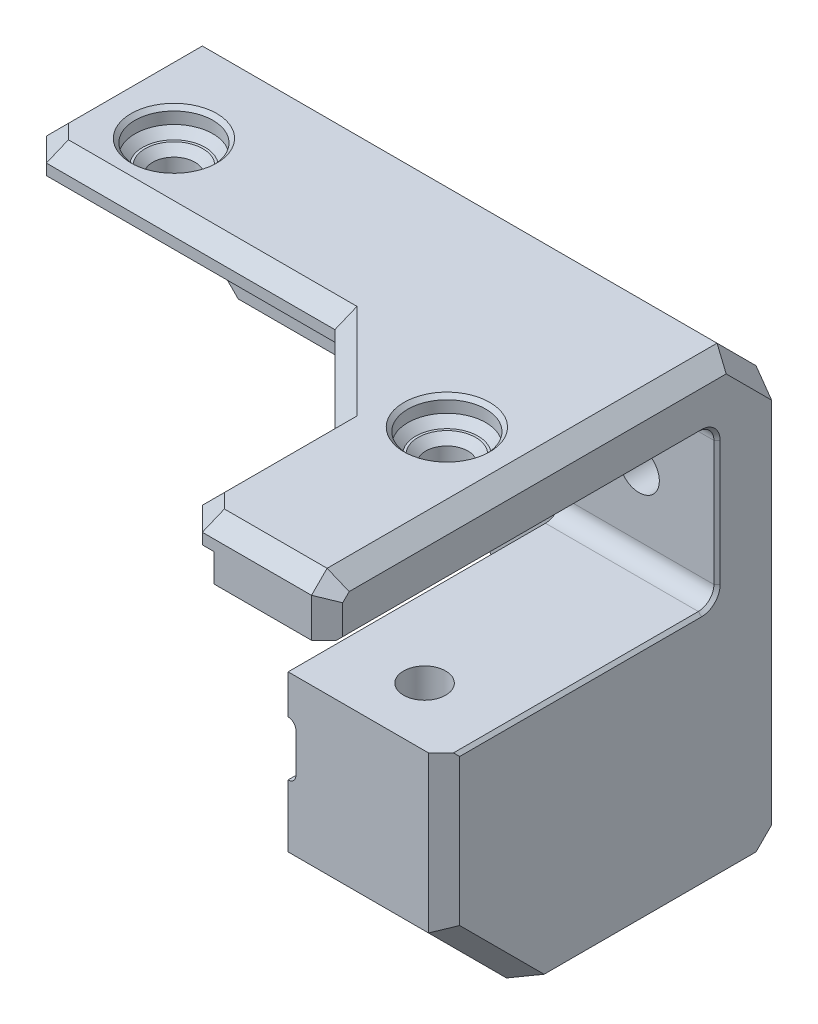
SolidWorks part; units mm, degrees
other "Markup1"
sketch "Sketch11" plane through (35, 3.4, 35) normal (0.3457, 0.6994, 0.6255) x (0.9247, -0.1409, -0.3536)
ref_plane "Front Plane" through (0, 0, 0) normal (0, 0, 1) x (1, 0, 0)
ref_plane "Top Plane" through (0, 0, 0) normal (0, 1, 0) x (1, 0, 0)
ref_plane "Right Plane" through (0, 0, 0) normal (1, 0, 0) x (0, 0, -1)
sketch "Sketch1" plane through (0, 0, 0) normal (0, 1, 0) x (1, 0, 0)
  line L1 (-35, -25) -> (35, -25)
  line L2 (-35, -25) -> (-35, 25)
  line L3 (-35, 25) -> (35, 25)
  line L4 (35, -25) -> (35, 25)
  line L5 (-35, -25) -> (35, 25) construction
  line L6 (-35, 25) -> (35, -25) construction
  point P0 (0, 0)
  dimension "D1" = 70
  dimension "D2" = 50
extrude "Boss-Extrude1" add sketch "Sketch1" along normal blind 3.4
sketch "Sketch2" plane through (0, 0, 0) normal (0, -1, 0) x (1, 0, 0)
  line L0 (-35, -10.5) -> (-35, -25)
  line L1 (-35, -25) -> (-35, 25) construction
  line L2 (-35, -25) -> (35, -25)
  line L3 (35, -25) -> (35, 25)
  line L4 (35, 25) -> (20.5, 25)
  line L5 (-35, 25) -> (35, 25) construction
  line L6 (20.5, 25) -> (20.5, -10.5)
  line L7 (20.5, -10.5) -> (-35, -10.5)
  dimension "D1" = 14.5
  dimension "D2" = 14.5
extrude "Boss-Extrude2" add sketch "Sketch2" along normal up to surface (3.6 mm away)
sketch "Sketch3" plane through (0, 3.4, 0) normal (0, 1, 0) x (1, 0, 0)
  line L0 (16, -25) -> (16, -5)
  line L1 (-35, -25) -> (35, -25) construction
  line L2 (16, -5) -> (5, 6)
  line L3 (5, 6) -> (-35, 6)
  line L4 (-35, 25) -> (-35, -25) construction
  line L5 (-35, 6) -> (-35, -25)
  line L6 (-35, -25) -> (16, -25)
  dimension "D1" = 19
  dimension "D2" = 19
  dimension "D3" = 20
  dimension "D4" = 40
extrude "Cut-Extrude1" cut sketch "Sketch3" against normal through all
sketch "Sketch4" plane through (0, 0, -25) normal (0, 0, -1) x (-1, 0, 0)
  line L4 (-35, -3.6) -> (-35, -53.6)
  line L5 (-35, -53.6) -> (35, -53.6)
  line L6 (35, -53.6) -> (35, -3.6)
  line L8 (-35, 3.4) -> (-35, -3.6)
  line L9 (-35, -3.6) -> (35, -3.6)
  line L10 (35, -3.6) -> (35, 3.4)
  line L11 (35, 3.4) -> (-35, 3.4)
  line L12 (-35, 3.4) -> (-35, -3.6)
  line L14 (35, -3.6) -> (35, 3.4)
  line L15 (35, 3.4) -> (-35, 3.4)
  dimension "D2" = 50
  dimension "D1" = 0
extrude "Boss-Extrude3" add sketch "Sketch4" along normal blind 7
fillet "Fillet1" radius 2 1 edges at (0, -3.6, -25)
sketch "Sketch5" plane through (0, 3.4, 0) normal (0, 1, 0) x (1, 0, 0)
  circle A0 centre (25, 0.3579) radius 5
  circle A1 centre (-24.571, 14.9289) radius 5
  dimension "D1" = 10
extrude "Cut-Extrude2" cut sketch "Sketch5" against normal blind 3
chamfer "Chamfer9" distance 0.5 angle 45 2 edges at (-24.571, 3.4, -9.9289) (25, 3.4, 4.6421)
chamfer "Chamfer10" distance 1 angle 45 2 edges at (-24.571, 0.4, -9.9289) (25, 0.4, 4.6421)
sketch "Sketch12" plane through (0, 0.4, 0) normal (0, 1, 0) x (1, 0, 0)
  circle A0 centre (-24.571, 14.9289) radius 2.7
  circle A1 centre (25, 0.3579) radius 2.7
  dimension "D1" = 5.4
extrude "Cut-Extrude4" cut sketch "Sketch12" against normal through all
chamfer "Chamfer12" distance 1 angle 45 2 edges at (-24.571, 0.4, -12.2289) (25, 0.4, 2.3421)
chamfer "Chamfer2" distance 3 angle 45 3 edges at (-35, 1.7, -6) (16, 1.7, 25) (-35, -53.6, -28.5)
chamfer "Chamfer13" distance 2 angle 45 10 edges at (1.5, -53.6, -32) (27, 3.4, 25) (17.5, 3.4, 23.5) (16, 3.4, 13.5) (10.5, 3.4, -0.5) (-13.5, 3.4, -6) (-33.5, 3.4, -7.5) (-35, 3.4, -20.5) (-35, -23.6, -32) (-33.5, -52.1, -25)
chamfer "Chamfer14" distance 5 angle 45 1 edges at (1, 3.4, -32)
ref_plane "Plane1" through (0, -25, 0) normal (0, 1, 0) x (1, 0, 0)
sketch "Sketch14" plane through (0, 0, -25) normal (0, 0, 1) x (1, 0, 0)
  line L0 (-35, -3.6) -> (35, -3.6) construction
  line L1 (35, -53.6) -> (15, -53.6)
  line L2 (35, -53.6) -> (35, -23.6)
  line L3 (35, -23.6) -> (15, -23.6)
  line L4 (15, -53.6) -> (15, -23.6)
  dimension "D1" = 20
  dimension "D2" = 30
  dimension "D3" = 20
extrude "Boss-Extrude4" add sketch "Sketch14" along normal blind 35 separate body
sketch "Sketch16" plane through (35, 0, 0) normal (1, 0, 0) x (0, 0, -1)
  line L14 (-10, -53.6) -> (-10, -23.6) construction
  line L15 (-10, -43.6) -> (0, -53.6)
  line L16 (-10, -53.6) -> (25, -53.6) construction
  line L17 (0, -53.6) -> (25, -53.6)
  line L26 (-10, -43.6) -> (-10, -53.6)
  line L27 (-10, -53.6) -> (0, -53.6)
  line M7 (-10, -23.6) -> (-10, -53.6)
  line M8 (-10, -53.6) -> (25, -53.6)
  dimension "D1" = 10
  dimension "D2" = 10
extrude "Cut-Extrude5" cut sketch "Sketch16" against normal through all contours L15 M7 M8 | L27 L26 L15 region at (35, -50.2667, 6.6667)
sketch "Sketch18" plane through (0, -23.6, 0) normal (0, 1, 0) x (1, 0, 0)
  line L0 (25, -10) -> (25, -2.5) construction
  line L3 (35, -10) -> (15, -10) construction
  circle A0 centre (25, -2.5) radius 2.7
  dimension "D1" = 5.4
  dimension "D2" = 7.5
extrude "Cut-Extrude6" cut sketch "Sketch18" against normal through all
sketch "Sketch19" plane through (0, -53.6, 0) normal (0, -1, 0) x (1, 0, 0)
  circle A0 centre (25, 2.5) radius 5
  dimension "D1" = 10
extrude "Cut-Extrude7" cut sketch "Sketch19" against normal blind 10
sketch "Sketch21" plane through (0, 0, -32) normal (0, 0, -1) x (-1, 0, 0)
  line L0 (-25, -13.6) -> (-35, -13.6) construction
  line L1 (-35, -1.6) -> (-35, -51.6) construction
  line L2 (-25, -13.6) -> (-25, -1.6) construction
  line L3 (33, -1.6) -> (-35, -1.6) construction
  line L4 (-25, -13.6) -> (-25, -45.35) construction
  circle A0 centre (-25, -13.6) radius 2.6
  circle A1 centre (-25, -45.35) radius 2.6
  dimension "D1" = 5.2
  dimension "D2" = 10
  dimension "D3" = 12
  dimension "D4" = 31.75
extrude "Cut-Extrude8" cut sketch "Sketch21" against normal blind 10
sketch "Sketch22" plane through (0, 0, 10) normal (0, 0, 1) x (1, 0, 0)
  line L0 (15, -28.6) -> (16, -28.6)
  line L1 (15, -23.6) -> (15, -43.6) construction
  line L2 (16, -28.6) -> (16, -35.6)
  line L3 (16, -35.6) -> (15, -35.6)
  line L4 (15, -35.6) -> (15, -28.6)
  line L5 (15, -35.6) -> (16, -28.6) construction
  line L6 (16, -35.6) -> (15, -28.6) construction
  line L7 (35, -23.6) -> (15, -23.6) construction
  point P6 (15.5, -32.1)
  dimension "D1" = 7
  dimension "D2" = 1
  dimension "D3" = 8.5
extrude "Cut-Extrude9" cut sketch "Sketch22" against normal up to surface (35 mm away) contours L4 L0 L2 L3 up to face at (22.4, -13.6, -25)
combine bodies "Combine1" operation type add bodies to combine 116 114
fillet "Fillet3" radius 2 1 edges at (25, -23.6, -25)
chamfer "Chamfer15" distance 2 angle 45 6 edges at (35, -33.6, 10) (35, -48.6, 5) (35, 0.9, -29.5) (35, -1.1, 25) (35, 2.4, 24) (35, 3.4, -2)
chamfer "Chamfer17" distance 0.4 angle 45 5 edges at (35, -23.6, -7.5) (35, -23.0142, -24.4142) (35, -13.6, -25) (35, -4.1858, -24.4142) (35, -3.6, 0)
chamfer "Chamfer18" distance 0.5 angle 45 3 edges at (25, -53.6, -2.5) (25, -43.6, -2.5) (25, -43.6, -0.2)
sketch "Sketch24" plane through (0, 0, -32) normal (0, 0, -1) x (-1, 0, 0)
  line L0 (35, -23.99) -> (10, -23.99)
  line L2 (-10.03, -53.6) -> (35, -53.6)
  line L3 (35, -53.6) -> (35, -23.99)
  line L4 (33, -1.6) -> (-33, -1.6) construction
  line L6 (-35, -4.4284) -> (-35, -51.6) construction
  line L7 (-10.03, -53.6) -> (-10.03, -43.6)
  line L8 (-10.03, -43.6) -> (10, -23.99)
  dimension "D1" = 22.39
  dimension "D2" = 25
  dimension "D3" = 29.61
  dimension "D4" = 45.03
  dimension "D5" = 70
  dimension "D6" = 10
extrude "Cut-Extrude10" cut sketch "Sketch24" against normal blind 10
fillet "Fillet2" radius 1 2 edges at (16, -28.6, -7.5) (16, -35.6, -7.5)
fillet "Fillet4" radius 5 2 edges at (10.03, -43.6, -28.5) (-10, -23.99, -28.5)
chamfer "Chamfer20" distance 2 angle 45 5 edges at (10.03, -48.6511, -32) (9.6392, -43.7643, -32) (-0.0072, -33.7733, -32) (-10.1512, -24.3605, -32) (-22.5201, -23.99, -32)
chamfer "Chamfer21" distance 5 angle 45 2 edges at (10.03, -53.6, -27.5) (-35, -23.99, -27.5)
fillet "Fillet5" radius 2 1 edges at (10.03, -48.6, -27.5)
chamfer "Chamfer19" distance 2 angle 45 3 edges at (-35, 0.9, -29.5) (12.53, -51.1, -32) (-32.5, -21.49, -32)
sketch "Sketch25" plane through (0, 0, -25) normal (0, 0, 1) x (1, 0, 0)
  line L0 (-35, -18.99) -> (-35, -5.6) construction
  line L1 (-35, -18.99) -> (15, -18.99)
  line L2 (-35, -18.99) -> (-35, -53.57)
  line L3 (-35, -53.57) -> (15, -53.57)
  line L4 (15, -18.99) -> (15, -53.57)
  line L5 (10.6158, -49.1858) -> (15, -53.57) construction
  line L6 (-30, -23.99) -> (-12.0401, -23.99) construction
  dimension "D1" = 5
  dimension "D2" = 0
extrude "Cut-Extrude11" cut sketch "Sketch25" against normal blind 3.6
